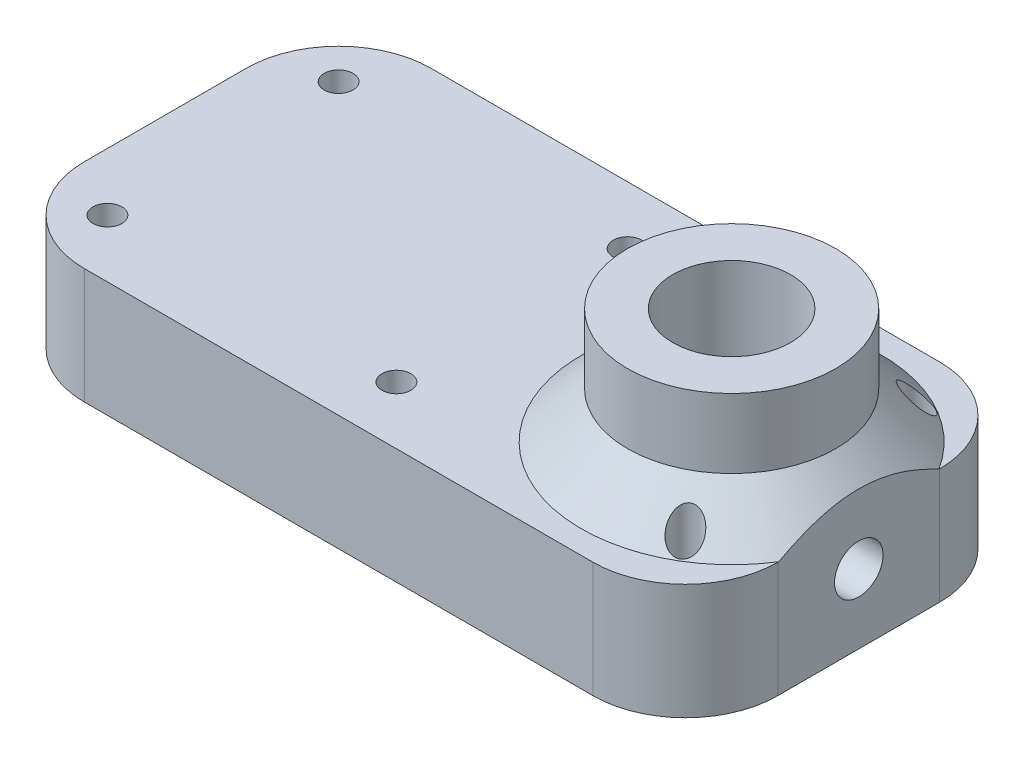
SolidWorks part; units mm, degrees
material "Aluminum 101"
ref_plane "Front Plane" through (0, 0, 0) normal (0, 0, 1) x (1, 0, 0)
ref_plane "Top Plane" through (0, 0, 0) normal (0, 1, 0) x (1, 0, 0)
ref_plane "Right Plane" through (0, 0, 0) normal (1, 0, 0) x (0, 0, -1)
sketch "Sketch1" plane through (0, 0, 0) normal (0, 1, 0) x (1, 0, 0)
  line L1 (-49, 15) -> (11, 15)
  line L2 (-49, 15) -> (-49, -15)
  line L3 (-49, -15) -> (11, -15)
  line L4 (11, 15) -> (11, -15)
  circle A1 centre (0, 0) radius 9
  point P8 (11, 0)
  dimension "D2" = 18
  dimension "D3" = 30
  dimension "D4" = 60
  dimension "D1" = 11
extrude "Base" add sketch "Sketch1" along normal blind 10 contours L4 A1 L1 L2 L3 | A1 region at (-22.1283, 0, 0) region at (0, 0, 0)
fillet "AddALittleBeauty" radius 8 4 edges at (-49, 5, 15) (-49, 5, -15) (11, 5, -15) (11, 5, 15)
extrude "RodHolder" add sketch "Sketch1<3>" along normal blind 20 contours A1 region at (0, 0, 0)
sketch "Sketch1<3>" plane through (0, 0, 0) normal (0, 1, 0) x (1, 0, 0) same geometry as "Sketch1"
hole_wizard "M5x0.8 Tapped Hole for fixing rod" positions "Sketch3" profile "Sketch4" tap size "M5x0.8" standard "ANSI Metric"
sketch "Sketch3" plane through (11, 0, 0) normal (1, 0, 0) x (0, 0, -1)
  line L0 (7, 0) -> (-7, 0) construction
  point P0 (0, 6)
  dimension "D1" = 6
cosmetic thread "Hole Thread1" parameters "D1"=6.3524, "D2"=5
sketch "Sketch4" plane through (11, 6, 0) normal (0, 1, 0) x (0, 0, -1)
  line L0 (0, 0) -> (0, 11.6618)
  line L1 (0, 11.6618) -> (2.1, 10.4)
  line L2 (2.1, 10.4) -> (2.1, 0)
  line L5 (2.1, 0) -> (0, 0)
  line L10 (0, 11.6618) -> (-2.1, 10.4) construction
  line L11 (0, -6.35) -> (0, 107.95) construction
  dimension "Tap Drill Dia." = 4.2
  dimension "Tap Drill Depth" = 10.4
  dimension "Drill Angle" = 118
chamfer "Chamfer1" distance 4 angle 45 1 edges at (0, 10, 9)
hole_wizard "Ø10.2 (10.2) Rod Hole" positions "Sketch5" profile "Sketch6" hole size "Ø10.2" standard "ANSI Metric" end condition through all
sketch "Sketch5" plane through (0, 20, 0) normal (0, 1, 0) x (1, 0, 0)
  point P0 (0, 0)
sketch "Sketch6" plane through (0, 20, 0) normal (1, 0, 0) x (0, 0, 1)
  line L0 (0, 0) -> (0, 20)
  line L1 (0, 20) -> (5.1, 20)
  line L2 (5.1, 20) -> (5.1, 0)
  line L5 (5.1, 0) -> (0, 0)
  line L11 (0, -6.35) -> (0, 107.95) construction
  dimension "Thru Hole Dia." = 10.2
  dimension "Thru Hole Depth" = 20
hole_wizard "M3x0.5 Tapped Hole1" positions "Sketch7" profile "Sketch8" tap size "M3x0.5" standard "ANSI Metric" end condition through all
sketch "Sketch7" plane through (0, 0, 0) normal (0, -1, 0) x (-1, 0, 0)
  line L0 (41, 15) -> (-3, 15) construction
  line L2 (49, 7) -> (49, -7) construction
  line L4 (19, 18.3865) -> (19, -17.1189) construction
  line L5 (49, 0) -> (41.0253, 0) construction
  point P0 (-6, 10)
  point P3 (-6, -10)
  point P6 (44, -10)
  point P9 (44, 10)
  point P27 (19, 10)
  point P29 (19, -10)
  point P39 (19, 15)
  point P45 (0, 0)
  dimension "D1" = 20
  dimension "D2" = 25
  dimension "D3" = 25
sketch "Sketch8" plane through (6, 0, -10) normal (1, 0, 0) x (0, 0, -1)
  line L0 (0, 0) -> (0, 20)
  line L1 (0, 20) -> (1.25, 20)
  line L2 (1.25, 20) -> (1.25, 0.275)
  line L3 (1.25, 0.275) -> (1.525, 0)
  line L5 (1.525, 0) -> (0, 0)
  line L6 (-1.25, 0.275) -> (-1.525, 0) construction
  line L11 (0, -6.35) -> (0, 107.95) construction
  dimension "Thru Tap Drill Dia." = 2.5
  dimension "Thru Tap Drill Depth" = 20
  dimension "Near C'Sink Dia." = 3.05
  dimension "Near C'Sink Angle" = 90
cosmetic thread "Hole Thread2" parameters "D2"=3
cosmetic thread "Hole Thread3" parameters "D2"=3
cosmetic thread "Hole Thread4" parameters "D2"=3
cosmetic thread "Hole Thread5" parameters "D2"=3
cosmetic thread "Hole Thread6" parameters "D2"=3
cosmetic thread "Hole Thread7" parameters "D2"=3
equation "\"D2@Sketch1\"=10.00mm+8"
